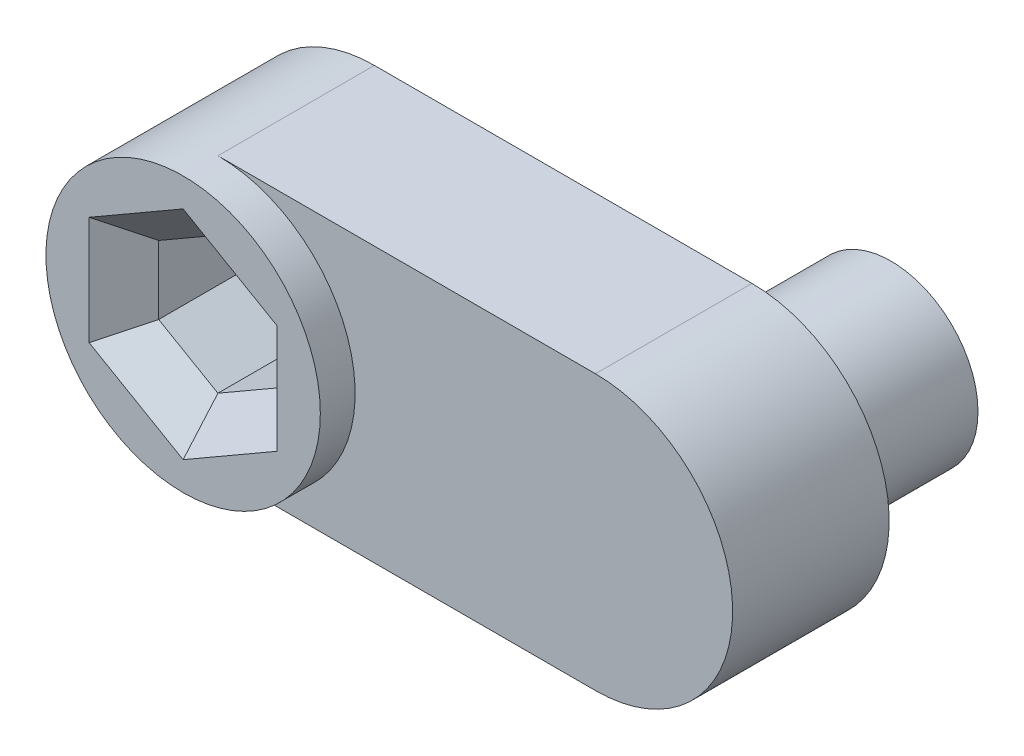
SolidWorks part; units mm, degrees
ref_plane "Plan de face" through (0, 0, 0) normal (1, 0, 0) x (0, 1, 0)
ref_plane "Plan de dessus" through (0, 0, 0) normal (0, 0, 1) x (0, 1, 0)
ref_plane "Plan de droite" through (0, 0, 0) normal (0, 1, 0) x (-1, 0, 0)
sketch "Esquisse1" plane through (0, 0, 0) normal (0, 0, 1) x (0, 1, 0)
  line L0 (0, -10.855) -> (0, 10.855) construction
  line L1 (-7.89, -10.855) -> (-7.89, 10.855)
  line L2 (7.89, -10.855) -> (7.89, 10.855)
  arc A0 (-7.89, -10.855) -> (7.89, -10.855) centre (0, -10.855) ccw
  arc A1 (7.89, 10.855) -> (-7.89, 10.855) centre (0, 10.855) ccw
  point P2 (0, 0)
  dimension "D2" = 15.78
  dimension "D1" = 21.71
extrude "Boss.-Extru.1" add sketch "Esquisse1" along normal blind 9
sketch "Esquisse3" plane through (0, 0, 0) normal (0, 0, -1) x (1, 0, 0)
  circle A0 centre (10.855, 0) radius 5
  arc A1 (10.855, -7.89) -> (10.855, 7.89) centre (10.855, 0) ccw construction
  dimension "D1" = 10
extrude "Boss.-Extru.3" add sketch "Esquisse3" along normal blind 8
sketch "Esquisse2" plane through (0, 0, 9) normal (0, 0, 1) x (1, 0, 0)
  line L1 (-10.855, 3.935) -> (-14.2628, 1.9675)
  line L2 (-14.2628, 1.9675) -> (-14.2628, -1.9675)
  line L3 (-14.2628, -1.9675) -> (-10.855, -3.935)
  line L4 (-10.855, -3.935) -> (-7.4472, -1.9675)
  line L5 (-7.4472, -1.9675) -> (-7.4472, 1.9675)
  line L6 (-7.4472, 1.9675) -> (-10.855, 3.935)
  circle A0 centre (-10.855, 0) radius 3.935 construction
  circle A1 centre (-10.855, 0) radius 3.4078 construction
  dimension "D1" = 7.87
extrude "Enlèv. mat.-Extru.1" cut sketch "Esquisse2" against normal through all contours L6 L1 L2 L3 L4 L5
sketch "Esquisse4" plane through (0, 0, 0) normal (0, 0, -1) x (1, 0, 0)
  line L38 (-5.4472, -3.1222) -> (-5.4472, 3.1222)
  line L39 (-10.855, -6.2444) -> (-5.4472, -3.1222)
  line L40 (-16.2628, -3.1222) -> (-10.855, -6.2444)
  line L41 (-16.2628, 3.1222) -> (-16.2628, -3.1222)
  line L42 (-10.855, 6.2444) -> (-16.2628, 3.1222)
  line L43 (-5.4472, 3.1222) -> (-10.855, 6.2444)
  line L44 (-5.4472, -3.1222) -> (-5.4472, 3.1222)
  line L45 (-10.855, -6.2444) -> (-5.4472, -3.1222)
  line L46 (-16.2628, -3.1222) -> (-10.855, -6.2444)
  line L47 (-16.2628, 3.1222) -> (-16.2628, -3.1222)
  line L48 (-10.855, 6.2444) -> (-16.2628, 3.1222)
  line L49 (-5.4472, 3.1222) -> (-10.855, 6.2444)
  dimension "D1" = 2
extrude "Enlèv. mat.-Extru.2" cut sketch "Esquisse4" against normal blind 2
sketch "Esquisse5" plane through (0, 0, 9) normal (0, 0, 1) x (1, 0, 0)
  circle A0 centre (-10.855, 0) radius 7.89
  arc A1 (-10.855, 7.89) -> (-10.855, -7.89) centre (-10.855, 0) ccw construction
  line M1 (-7.4472, 1.9675) -> (-7.4472, -1.9675)
  line M2 (-7.4472, -1.9675) -> (-10.855, -3.935)
  line M3 (-10.855, -3.935) -> (-14.2628, -1.9675)
  line M4 (-14.2628, -1.9675) -> (-14.2628, 1.9675)
  line M5 (-14.2628, 1.9675) -> (-10.855, 3.935)
  line M6 (-10.855, 3.935) -> (-7.4472, 1.9675)
  arc M9 (-10.855, 7.89) -> (-10.855, -7.89) centre (-10.855, 0) ccw
extrude "Boss.-Extru.4" add sketch "Esquisse5" along normal blind 2 contours A0 M9 M6 M1 M2 M3 M4 M5 region at (-5.4337, -5.4213, 9)
chamfer "Chanfrein1" distance 2 angle 45 6 edges at (-12.5589, 2.9512, 11) (-14.2628, 0, 11) (-12.5589, -2.9512, 11) (-9.1511, -2.9512, 11) (-7.4472, 0, 11) (-9.1511, 2.9512, 11)
